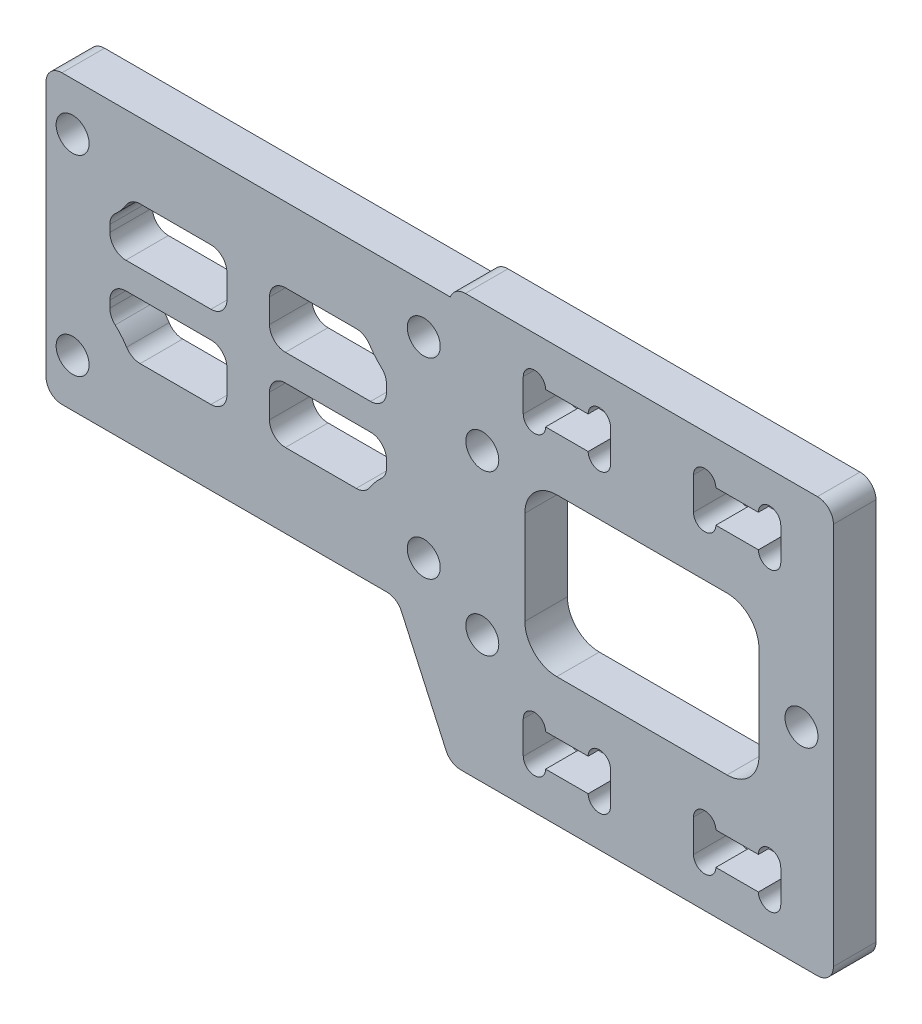
SolidWorks part; units mm, degrees
material "Thornel Mat VMA"
ref_plane "前视基准面" through (0, 0, 0) normal (0, 0, 1) x (1, 0, 0)
ref_plane "上视基准面" through (0, 0, 0) normal (0, 1, 0) x (1, 0, 0)
ref_plane "右视基准面" through (0, 0, 0) normal (1, 0, 0) x (0, 0, -1)
sketch "草图1" plane through (0, 0, 0) normal (0, 0, 1) x (1, 0, 0)
  line L0 (19, 7.4) -> (55, 7.4) construction
  line L1 (16.5, -9) -> (-16.5, -9) construction
  line L2 (16.5, -9) -> (16.5, 9) construction
  line L3 (16.5, 9) -> (-16.5, 9) construction
  line L4 (-16.5, -9) -> (-16.5, 9) construction
  line L5 (16.5, -9) -> (-16.5, 9) construction
  line L6 (16.5, 9) -> (-16.5, -9) construction
  line L8 (19, -14.25) -> (19, 13.5) construction
  line L9 (19, 13.5) -> (-18, 13.5)
  line L10 (-18, -12.7895) -> (-18, 13.5) construction
  line L11 (19, -14.25) -> (-18, 13.5) construction
  line L12 (19, 13.5) -> (-18, -12.7895) construction
  line L13 (55, 7.4) -> (55, -17.4)
  line L14 (55, -17.4) -> (16.5, -17.4) construction
  line L15 (29.95, 10.45) -> (29.95, 4.266) construction
  line L16 (-13, -4.1266) -> (-13, -1.25)
  line L22 (25.85, 7.4) -> (34.05, 7.4)
  line L27 (25.85, 7.4) -> (25.85, 10.45)
  line L28 (25.85, 10.45) -> (34.05, 10.45)
  line L29 (11.0456, -6.5) -> (2, -6.5)
  line L30 (13, -4.1266) -> (13, -1.25)
  line L31 (11.0456, 6.5) -> (2, 6.5)
  line L32 (-13, -6.5) -> (-13, -7.0909) construction
  line L33 (13, -6.5) -> (-13, 6.5) construction
  line L34 (13, 6.5) -> (-13, -6.5) construction
  line L35 (-2, 6.5) -> (-2, 1.25)
  line L36 (2, 6.5) -> (2, 1.25)
  line L37 (-2, 6.5) -> (-11.0456, 6.5)
  line L38 (-2, -6.5) -> (-11.0456, -6.5)
  line L40 (34.05, 7.4) -> (34.05, 10.45)
  line L41 (41.85, 7.4) -> (50.05, 7.4)
  line L42 (41.85, 7.4) -> (41.85, 10.45)
  line L43 (41.85, 10.45) -> (50.05, 10.45)
  line L44 (50.05, 7.4) -> (50.05, 10.45)
  line L45 (55, 14.5) -> (55, 7.4)
  line L46 (55, -5) -> (38.55, -5) construction
  line L47 (19, -24.5) -> (55, -24.5)
  line L48 (55, -24.5) -> (55, -17.4)
  line L49 (50.05, -17.4) -> (50.05, -20.45)
  line L50 (41.85, -20.45) -> (50.05, -20.45)
  line L51 (41.85, -17.4) -> (41.85, -20.45)
  line L52 (41.85, -17.4) -> (50.05, -17.4)
  line L53 (34.05, -17.4) -> (34.05, -20.45)
  line L54 (25.85, -20.45) -> (34.05, -20.45)
  line L55 (25.85, -17.4) -> (25.85, -20.45)
  line L56 (25.85, -17.4) -> (34.05, -17.4)
  line L58 (19, 13.5) -> (19, 14.5)
  line L59 (48, -12.4) -> (26, -12.4)
  line L60 (48, -12.4) -> (48, 2.4)
  line L61 (48, 2.4) -> (26, 2.4)
  line L62 (26, -12.4) -> (26, 2.4)
  line L63 (48, -12.4) -> (26, 2.4) construction
  line L64 (48, 2.4) -> (26, -12.4) construction
  line L65 (19, 14.5) -> (55, 14.5)
  line L71 (16.5, 0) -> (19, 0) construction
  line L72 (50.05, 8.925) -> (50.678, 8.925) construction
  line L73 (50.05, -18.925) -> (49.5, -18.925) construction
  line L82 (11.0456, 6.5) -> (11.0456, 13.5) construction
  line L83 (11.0456, -6.5) -> (11.0456, -1) construction
  line L84 (45.95, 10.45) -> (45.95, 4.266) construction
  line L89 (-18, 13.5) -> (-19, 13.5)
  line L90 (-19, 13.5) -> (-19, -13.5)
  line L92 (25.85, 8.925) -> (23.1613, 8.925) construction
  line L96 (-16.5, -9) -> (-16.5, -18) construction
  line L97 (14, -13.5) -> (-19, -13.5)
  line L102 (19, -24.5) -> (14, -13.5)
  line L103 (13, 1.25) -> (2, 1.25)
  line L105 (-13, 1.25) -> (-2, 1.25)
  line L107 (13, -1.25) -> (2, -1.25)
  line L108 (-2, -1.25) -> (-13, -1.25)
  line L110 (0, 0) -> (-5.8842, 0) construction
  line L112 (13, 1.25) -> (13, 4.1266)
  line L113 (-13, 1.25) -> (-13, 4.1266)
  line L114 (2, -1.25) -> (2, -6.5)
  line L115 (-2, -1.25) -> (-2, -6.5)
  circle A0 centre (-16.5, 9) radius 1.55
  circle A1 centre (-16.5, -9) radius 1.55
  circle A2 centre (16.5, 9) radius 1.55
  circle A3 centre (16.5, -9) radius 1.55
  arc A4 (-13, 4.1266) -> (-11.0456, 6.5) centre (-16.5, 9) ccw
  arc A5 (-11.0456, -6.5) -> (-13, -4.1266) centre (-16.5, -9) ccw
  arc A6 (13, -4.1266) -> (11.0456, -6.5) centre (16.5, -9) ccw
  arc A7 (11.0456, 6.5) -> (13, 4.1266) centre (16.5, 9) ccw
  circle A8 centre (26.9, 7.4) radius 1.05
  circle A9 centre (26.9, 10.45) radius 1.05
  circle A10 centre (33, 10.45) radius 1.05
  circle A11 centre (33, 7.4) radius 1.05
  circle A12 centre (42.9, 10.45) radius 1.05
  circle A13 centre (42.9, 7.4) radius 1.05
  circle A14 centre (49, 10.45) radius 1.05
  circle A15 centre (49, 7.4) radius 1.05
  circle A16 centre (49, -17.4) radius 1.05
  circle A17 centre (49, -20.45) radius 1.05
  circle A18 centre (42.9, -17.4) radius 1.05
  circle A19 centre (42.9, -20.45) radius 1.05
  circle A20 centre (33, -17.4) radius 1.05
  circle A21 centre (33, -20.45) radius 1.05
  circle A22 centre (26.9, -20.45) radius 1.05
  circle A23 centre (26.9, -17.4) radius 1.05
  circle A24 centre (22, -5) radius 1.55 construction
  circle A25 centre (52, -5) radius 1.55
  circle A26 centre (22, 2.5) radius 1.55
  circle A27 centre (22, -12.5) radius 1.55
  point P0 (0, 0)
  point P10 (0, 0)
  point P29 (0, 0)
  point P44 (9.5, -10.75)
  point P96 (37, -5)
  point P114 (-8, -10.75)
  dimension "D3" = 3.1
  dimension "D9" = 12
  dimension "D18" = 2.1
  dimension "D19" = 2.1
  dimension "D21" = 3.1
  dimension "D1" = 18
  dimension "D2" = 33
  dimension "D4" = 3.05
  dimension "D5" = 2.5
  dimension "D6" = 4
  dimension "D7" = 7
  dimension "D8" = 5
  dimension "D10" = 27.85
  dimension "D11" = 10.95
  dimension "D12" = 8.2
  dimension "D13" = 16
  dimension "D14" = 8.2
  dimension "D15" = 36
  dimension "D16" = 2.5
  dimension "D17" = 6
  dimension "D20" = 1
  dimension "D22" = 18
  dimension "D23" = 3
  dimension "D24" = 39
  dimension "D25" = 5
  dimension "D26" = 4
  dimension "D27" = 4
  dimension "D28" = 5
  dimension "D29" = 4.5
  dimension "D30" = 30
  dimension "D31" = 2.5
  dimension "D32" = 7
  dimension "D33" = 4.5
  dimension "D34" = 15
  dimension "D35" = 2.5
  dimension "D36" = 2
extrude "凸台-拉伸1" add sketch "草图1" along normal blind 4 contours L47 L48 L13 L45 L9 L10 L90 A25 A24 A15 L41 A13 L42 A12 L43 A14 L44 A11 L22 A8 L27 A9 L28 A10 L40 A3 A2 A1 A0 L59 L62 L61 L60 L38 A5 L16 A4 L37 region at (20.104, -2.9529, 0)
fillet "圆角4" radius 3 4 edges at (26, 2.4, 2) (26, -12.4, 2) (48, -12.4, 2) (48, 2.4, 2)
fillet "圆角2" radius 1.5 27 edges at (55, -24.5, 2) (55, 14.5, 2) (19, 14.5, 2) (13, -4.1266, 2) (-2, 6.5, 2) (2, 6.5, 2) (-11.0456, 6.5, 2) (-11.0456, -6.5, 2) (-13, -4.1266, 2) (-19, 13.5, 2) (-19, -13.5, 2) (14, -13.5, 2) (19, -24.5, 2) (2, 1.25, 2) (13, 1.25, 2) (13, 4.1266, 2) (13, -1.25, 2) (2, -1.25, 2) (2, -6.5, 2) (11.0456, -6.5, 2) (-2, -6.5, 2) (-2, -1.25, 2) (-13, -1.25, 2) (-13, 1.25, 2) (-2, 1.25, 2) (-13, 4.1266, 2) (11.0456, 6.5, 2)
